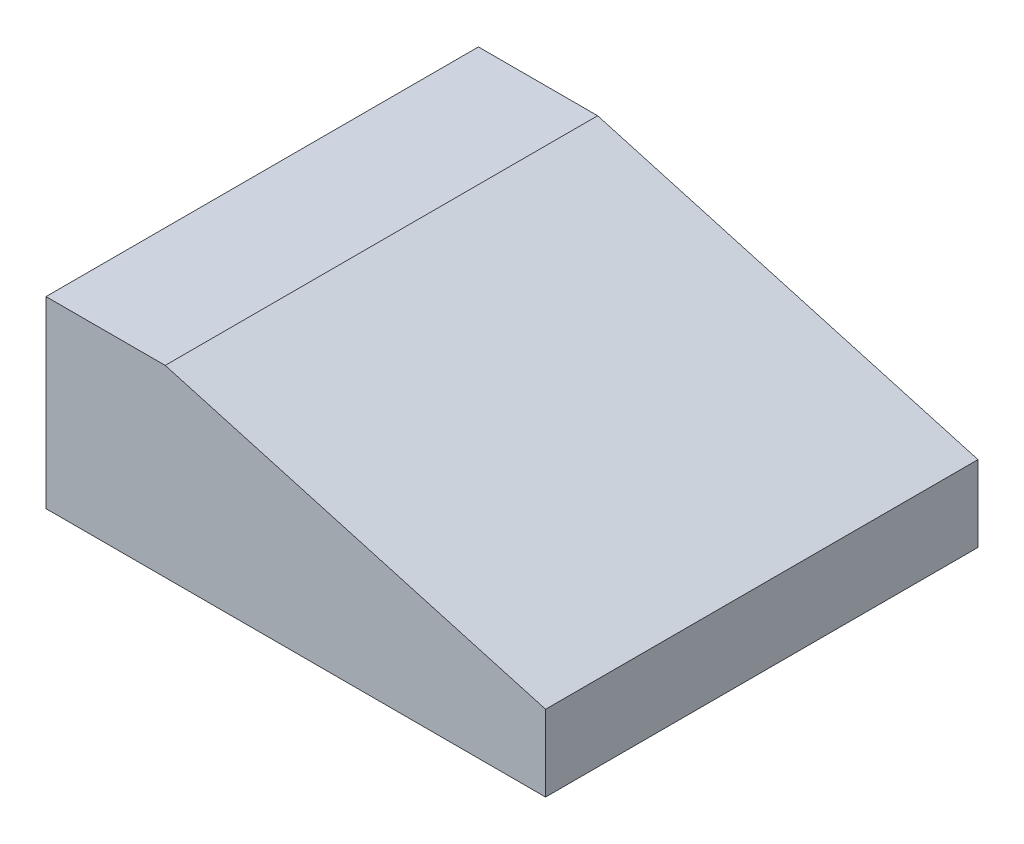
SolidWorks part; units mm, degrees
material "ABS"
ref_plane "Front Plane" through (0, 0, 0) normal (0, 0, 1) x (1, 0, 0)
ref_plane "Top Plane" through (0, 0, 0) normal (0, 1, 0) x (1, 0, 0)
ref_plane "Right Plane" through (0, 0, 0) normal (1, 0, 0) x (0, 0, -1)
sketch "Sketch1" plane through (0, 0, 0) normal (0, 0, 1) x (1, 0, 0)
  line L0 (0, 0) -> (0, 50.9723)
  line L1 (0, 50.9723) -> (33.0805, 50.9723)
  line L2 (33.0805, 50.9723) -> (138.6293, 21.1098)
  line L3 (138.6293, 21.1098) -> (138.6293, 0)
  line L4 (138.6293, 0) -> (0, 0)
extrude "Boss-Extrude1" add sketch "Sketch1" along normal blind 120
